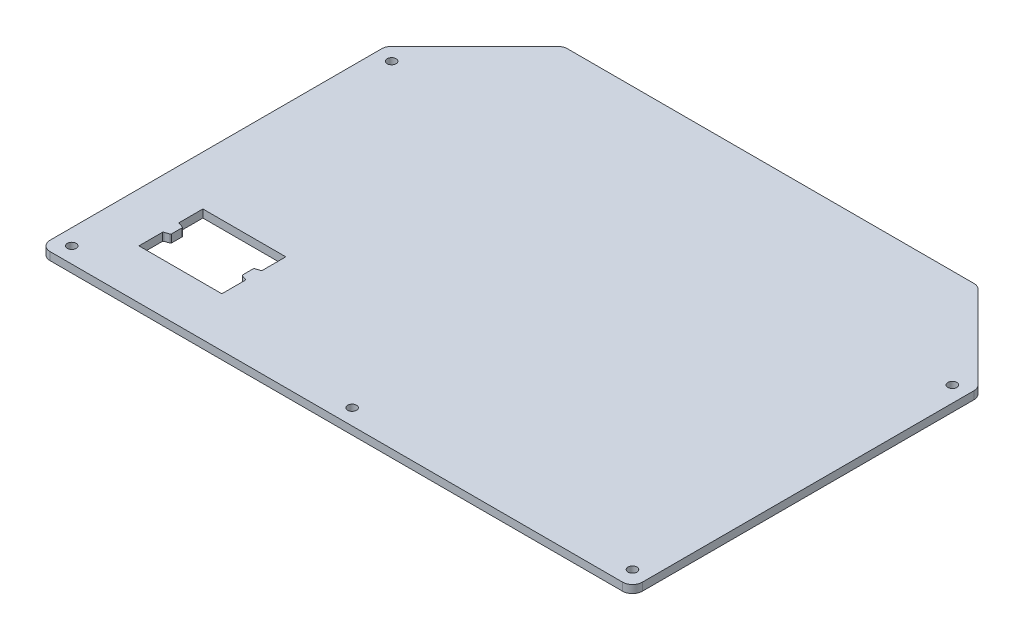
SolidWorks part; units mm, degrees
material "Acier non allié"
ref_plane "Front" through (0, 0, 0) normal (0, 0, 1) x (1, 0, 0)
ref_plane "Top" through (0, 0, 0) normal (0, 1, 0) x (1, 0, 0)
ref_plane "Right" through (0, 0, 0) normal (1, 0, 0) x (0, 0, -1)
sketch "Main scetch" plane through (0, 0, 0) normal (0, 1, 0) x (1, 0, 0)
  line L0 (-150, 0) -> (150, 0)
  line L1 (0, 0) -> (150, 0) construction
  line L2 (0, 0) -> (0, 220) construction
  line L3 (0, 220) -> (150, 220) construction
  line L4 (150, 0) -> (150, 220) construction
  line L5 (150, 0) -> (150, 175)
  line L6 (150, 175) -> (105, 220)
  line L10 (105, 220) -> (-105, 220)
  line L11 (-150, 0) -> (-150, 175)
  line L12 (-150, 175) -> (-105, 220)
  dimension "D1" = 150
  dimension "D2" = 220
  dimension "D3" = 45
  dimension "D4" = 45
extrude "Main extrusion" add sketch "Main scetch" along normal blind 4
fillet "Corner leave" radius 5 6 edges at (-150, 2, 0) (150, 2, -175) (105, 2, -220) (150, 2, 0) (-105, 2, -220) (-150, 2, -175)
sketch "Esquisse1" plane through (0, 4, 0) normal (0, 1, 0) x (1, 0, 0)
  line L0 (-145, 0) -> (145, 0) construction
  line L1 (-150, 172.9289) -> (-150, 5) construction
  line L3 (0, 0) -> (0, 62.3031) construction
  line L4 (150, 5) -> (150, 172.9289) construction
  circle A0 centre (-142, 8) radius 1
  circle A1 centre (-142, 170) radius 1
  circle A4 centre (142, 170) radius 1
  circle A5 centre (142, 8) radius 1
  circle A6 centre (0, 8) radius 1.5
  dimension "D3" = 2
  dimension "D6" = 2
  dimension "D8" = 8
  dimension "D15" = 2
  dimension "D18" = 2
  dimension "D7" = 3
  dimension "D1" = 8
  dimension "D2" = 8
  dimension "D4" = 8
  dimension "D5" = 170
  dimension "D13" = 170
  dimension "D14" = 8
  dimension "D16" = 8
  dimension "D17" = 8
hole_wizard "Dégagement M41" positions "Esquisse2" profile "Esquisse3" hole size "M4" standard "ISO" end condition through all
sketch "Esquisse2" plane through (0, 4, 0) normal (0, 1, 0) x (1, 0, 0)
  point P0 (-142, 8)
  point P3 (-142, 170)
  point P6 (142, 170)
  point P9 (142, 8)
  point P12 (0, 8)
sketch "Esquisse3" plane through (-142, 4, -8) normal (1, 0, 0) x (0, 0, 1)
  line L0 (0, 0) -> (0, 4)
  line L1 (0, 4) -> (2.25, 4)
  line L2 (2.25, 4) -> (2.25, 0)
  line L5 (2.25, 0) -> (0, 0)
  line L11 (0, -6.35) -> (0, 107.95) construction
  dimension "Diamètre du perçage jusqu'au prochain" = 4.5
  dimension "Profondeur du perçage jusqu'au prochain" = 4
sketch "Esquisse4" plane through (0, 4, 0) normal (0, 1, 0) x (1, 0, 0)
  line L0 (-125, 57.4) -> (-83, 25) construction
  line L1 (-125, 57.4) -> (-83, 57.4) construction
  line L2 (-125, 57.4) -> (-125, 25) construction
  line L3 (-125, 25) -> (-83, 25) construction
  line L4 (-83, 57.4) -> (-83, 25) construction
  line L5 (-125, 25) -> (-83, 57.4) construction
  line L6 (-145, 0) -> (145, 0) construction
  line L7 (-150, 172.9289) -> (-150, 5) construction
  line L8 (-125, 57.4) -> (-83, 57.4)
  line L9 (-83, 57.4) -> (-83, 45.2)
  line L10 (-83, 45.2) -> (-86, 44.2)
  line L11 (-86, 44.2) -> (-86, 38.2)
  line L12 (-86, 38.2) -> (-83, 37.2)
  line L13 (-83, 37.2) -> (-83, 25)
  line L14 (-83, 25) -> (-125, 25)
  line L15 (-125, 25) -> (-125, 37.2)
  line L16 (-125, 37.2) -> (-122, 38.2)
  line L17 (-122, 38.2) -> (-122, 44.2)
  line L18 (-122, 44.2) -> (-125, 45.2)
  line L19 (-125, 45.2) -> (-125, 57.4)
  line L20 (-104, 41.2) -> (-125, 41.2) construction
  line L21 (-104, 41.2) -> (-83, 41.2) construction
  point P15 (-86, 41.2)
  point P19 (0, 0)
  point P20 (-122, 41.2)
  dimension "D1" = 32.4
  dimension "D2" = 42
  dimension "D3" = 25
  dimension "D4" = 25
  dimension "D5" = 3
  dimension "D6" = 3
  dimension "D7" = 6
  dimension "D8" = 6
  dimension "D9" = 8
  dimension "D10" = 8
  dimension "D11" = 12.2
  dimension "D12" = 12.2
extrude "Enlèv. mat.-Extru.1" cut sketch "Esquisse4" against normal up to surface (4 mm away) up to face at (-142, 0, -5.75)
fillet "Congé1" radius 0.5 8 edges at (-83, 2, -37.2) (-86, 2, -38.2) (-86, 2, -44.2) (-83, 2, -45.2) (-122, 2, -44.2) (-125, 2, -45.2) (-122, 2, -38.2) (-125, 2, -37.2)
equation "\"WIDTH\"= 300mm'Total width of the robot"
equation "\"LENGTH\"= 220mm'Total length of the robot"
equation "\"D1@Main scetch\" = \"WIDTH\" / 2"
equation "\"D2@Main scetch\" = \"LENGTH\""
equation "\"CUT_DEPTH\"= 45mm'Depth of the cut on the edges of the plate"
equation "\"D3@Main scetch\" = \"CUT_DEPTH\""
equation "\"D4@Main scetch\" = \"CUT_DEPTH\""
equation "\"Plate_th\"= 3mm'Thickness of the plate"
equation "\"D1\"= \"Plate_th\""
